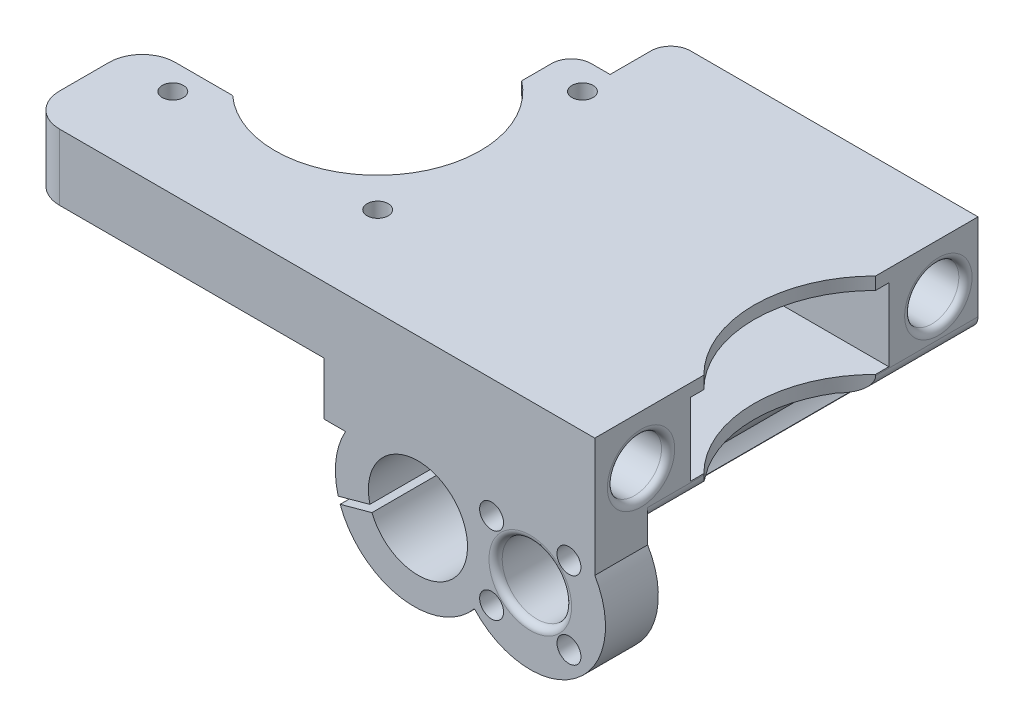
SolidWorks part; units mm, degrees
ref_plane "Alzado" through (0, 0, 0) normal (0, 0, 1) x (1, 0, 0)
ref_plane "Planta" through (0, 0, 0) normal (0, 1, 0) x (1, 0, 0)
ref_plane "Vista lateral" through (0, 0, 0) normal (1, 0, 0) x (0, 0, -1)
sketch "Croquis2" plane through (0, 0, 0) normal (0, 0, 1) x (1, 0, 0)
  line L0 (-3.0211, 10.5277) -> (-51.2966, 10.5277)
  line L2 (34.7034, 10.5277) -> (46.9364, 10.5277) construction
  line L4 (-13.6832, 10.5277) -> (-3.0211, 10.5277) construction
  line L6 (34.7034, 10.5277) -> (34.7034, 28.5277)
  line L7 (34.7034, 28.5277) -> (-51.2966, 28.5277)
  line L8 (-51.2966, 10.5277) -> (-51.2966, 28.5277)
  line L9 (-3.0211, 10.5277) -> (-13.6832, 10.5277) construction
  circle A0 centre (19.0834, 10.5277) radius 1.8114
  circle A1 centre (24.9386, 4.6724) radius 5
  circle A2 centre (30.7938, 10.5277) radius 1.8114
  circle A3 centre (19.0834, -1.1823) radius 1.81
  arc A4 (8.5391, -3.0676) -> (11.1821, 11.7271) centre (7.9425, 4.6724) ccw
  arc A5 (7.9391, -7.2159) -> (16.483, -2.9524) centre (7.3425, 4.6724) ccw
  arc A6 (34.7034, -1.1828) -> (16.483, 12.2973) centre (24.9386, 4.6724) ccw
  arc A7 (16.483, 12.2973) -> (11.7136, 15.7441) centre (7.3425, 4.6724) ccw
  arc A8 (9.846, 12.1984) -> (7.3459, -3.0676) centre (7.9425, 4.6724) ccw
  arc A9 (10.2612, 16.2123) -> (-3.0211, -1.1828) centre (7.3425, 4.6724) ccw
  circle A10 centre (30.7938, -1.1828) radius 1.8114
  arc A11 (16.483, -2.9524) -> (16.483, 12.2973) centre (24.9386, 4.6724) ccw
  arc A12 (16.483, 12.2973) -> (6.7459, -7.2159) centre (7.3425, 4.6724) ccw
  arc A13 (8.5391, -3.0676) -> (7.3459, -3.0676) centre (7.9425, 4.6724) ccw
  circle A14 centre (7.9425, 4.6724) radius 7.763
  arc A15 (16.483, 12.2973) -> (16.483, -2.9524) centre (7.3425, 4.6724) ccw
  dimension "D3" = 11.7104
  dimension "D7" = 10
  dimension "D1" = 18
  dimension "D2" = 86
  dimension "D4" = 11.7104
  dimension "D5" = 11.7104
  dimension "D6" = 11.71
extrude "Saliente-Extruir2" add sketch "Croquis2" against normal blind 58 contours A12 A7 A6 L6 L7 L8 L0 A9 | A13 A4 A5 A11 A6 A7 A12 A9 A8 A0 A1 A2 A3 A10 region at (-11.0933, 20.3038, 0) region at (16.4486, 4.6722, 0)
sketch "Croquis3" plane through (0, 0, -58) normal (0, 0, -1) x (-1, 0, 0)
  line L0 (-36.4091, 13.5277) -> (-11.0589, 13.5277) construction
  line L1 (-32.0954, 13.5277) -> (-17.7818, 13.5277)
  arc A0 (-15.2982, 10.7303) -> (-17.7818, 13.5277) centre (-24.9386, 4.6724) ccw
  arc A2 (-15.263, 10.6739) -> (-17.7818, 13.5277) centre (-24.9386, 4.6724) ccw
  circle A3 centre (-30.7938, 10.5277) radius 1.8114 construction
  circle A4 centre (-30.7938, 10.5277) radius 1.8114
  arc A5 (-32.0954, 13.5277) -> (-15.2982, -1.3854) centre (-24.9386, 4.6724) ccw
  arc A6 (-32.0954, 13.5277) -> (-15.263, -1.329) centre (-24.9386, 4.6724) ccw
  arc A7 (-15.263, 10.6739) -> (-15.263, -1.329) centre (-7.9425, 4.6724) ccw
  arc M7 (-34.7034, 10.5277) -> (-16.483, -2.9524) centre (-24.9386, 4.6724) ccw
  circle M13 centre (-19.0834, 10.5277) radius 1.8114
  circle M14 centre (-24.9386, 4.6724) radius 5
  circle M15 centre (-30.7938, 10.5277) radius 1.8114
  circle M16 centre (-19.0834, -1.1823) radius 1.81
  circle M17 centre (-30.7938, -1.1828) radius 1.8114
  dimension "D1" = 3
sketch "Croquis4" plane through (34.7034, 0, 0) normal (1, 0, 0) x (0, 0, -1)
  line L0 (0, 10.5277) -> (0, 28.5277) construction
  line L1 (58, 28.5277) -> (0, 28.5277) construction
  line L3 (14.5, 26.6277) -> (44.5, 26.6277)
  line L4 (14.5, 26.6277) -> (14.5, 15.6277)
  line L5 (14.5, 15.6277) -> (44.5, 15.6277)
  line L6 (44.5, 26.6277) -> (44.5, 15.6277)
  circle A0 centre (7, 21.0777) radius 4.1
  circle A1 centre (52, 21.0777) radius 4.1
  dimension "D3" = 7.45
  dimension "D2" = 7.45
  dimension "D1" = 7
  dimension "D4" = 45
  dimension "D5" = 30
  dimension "D6" = 11
  dimension "D7" = 1.9
  dimension "D8" = 7.5
extrude "Cortar-Extruir4" cut sketch "Croquis4" against normal blind 87 contours L6 L3 L4 L5 region at (34.7034, 21.1277, -29.5)
sketch "Croquis6" plane through (0, 10.5277, 0) normal (0, -1, 0) x (1, 0, 0)
  line L1 (-51.2966, -44.5) -> (-51.2966, -19.5)
  line L5 (-12.7902, -14.6314) -> (-17.6588, -19.5) construction
  line L6 (-51.2966, -19.5) -> (-17.6588, -19.5)
  line L7 (-51.2966, -58) -> (-51.2966, 0) construction
  line L8 (-17.6588, -19.5) -> (-17.6588, -58)
  line L9 (-3.0211, -58) -> (-51.2966, -58) construction
  line L10 (-17.6588, -58) -> (-51.2966, -58)
  line L11 (-51.2966, -58) -> (-51.2966, -19.5)
  circle A0 centre (-42.6588, -13.5) radius 1.6
  circle A1 centre (-11.6588, -13.5) radius 1.6
  circle A2 centre (-11.6588, -44.5) radius 1.6
  line M8 (-51.2966, 0) -> (-51.2966, -58)
  line M9 (-51.2966, -58) -> (-3.0211, -58)
  dimension "D1" = 31
  dimension "D4" = 6
extrude "Cortar-Extruir5" cut sketch "Croquis6" against normal blind 18 contours L8 L6 M8 M9 | A1 | A0 | A2 region at (-34.4777, 10.5277, -38.75)
sketch "Croquis7" plane through (-17.6588, 0, 0) normal (-1, 0, 0) x (0, 0, 1)
  line L0 (-19.5, 15.6277) -> (-44.5, 15.6277) construction
  line L1 (-44.5, 26.6277) -> (-41.5, 26.6277)
  line L2 (-44.5, 26.6277) -> (-44.5, 15.6277)
  line L3 (-44.5, 15.6277) -> (-41.5, 15.6277)
  line L4 (-41.5, 26.6277) -> (-41.5, 15.6277)
  dimension "D1" = 3
extrude "Saliente-Extruir3" add sketch "Croquis7" against normal blind 12
sketch "Croquis8" plane through (-51.2966, 0, 0) normal (-1, 0, 0) x (0, 0, 1)
  line L0 (-14.5, 15.6277) -> (-19.5, 15.6277) construction
  line L1 (-14.5, 26.6277) -> (-17.5, 26.6277)
  line L2 (-14.5, 26.6277) -> (-14.5, 15.6277)
  line L3 (-14.5, 15.6277) -> (-17.5, 15.6277)
  line L4 (-17.5, 26.6277) -> (-17.5, 15.6277)
  dimension "D1" = 3
extrude "Saliente-Extruir4" add sketch "Croquis8" against normal blind 45
sketch "Croquis9" plane through (-51.2966, 0, 0) normal (-1, 0, 0) x (0, 0, 1)
  line L0 (0, 10.5277) -> (0, 28.5277) construction
  line L3 (-19.5, 18.5277) -> (0, 18.5277)
  line L6 (-19.5, 18.5277) -> (0, 18.5277)
  line L7 (-19.5, 18.5277) -> (-19.5, 10.5277)
  line L8 (-19.5, 10.5277) -> (0, 10.5277)
  line L9 (0, 18.5277) -> (0, 10.5277)
  line M2 (-17.5, 26.6277) -> (-17.5, 15.6277)
  line M3 (-17.5, 15.6277) -> (-19.5, 15.6277)
  line M4 (-19.5, 15.6277) -> (-19.5, 10.5277)
  line M5 (-19.5, 10.5277) -> (0, 10.5277)
  line M6 (0, 10.5277) -> (0, 28.5277)
extrude "Cortar-Extruir6" cut sketch "Croquis9" against normal blind 45 contours L3 M2 M3 M4 M5 M6 region at (-51.2966, 14.4292, -9.4121)
sketch "Croquis10" plane through (0, 10.5277, 0) normal (0, -1, 0) x (1, 0, 0)
  line L0 (-6.2966, -19.5) -> (-17.6588, -35.5392)
  line L1 (-17.6588, -19.5) -> (-17.6588, -58) construction
  line L2 (-17.6588, -35.5392) -> (-17.6588, -19.5)
  line L3 (-17.6588, -19.5) -> (-6.2966, -19.5)
extrude "Cortar-Extruir7" cut sketch "Croquis10" against normal blind 6
sketch "Croquis11" plane through (0, 10.5277, 0) normal (0, -1, 0) x (1, 0, 0)
  line L1 (-13.5623, -58) -> (-11.8001, -58)
  line L2 (-13.5623, -48.8189) -> (-17.6588, -48.8189)
  line L3 (-13.5623, -48.8189) -> (-11.8001, -48.8189)
  line L6 (-17.6588, -35.5392) -> (-17.6588, -58) construction
  line L7 (-17.6588, -48.8189) -> (-17.6588, -58)
  line L8 (-17.6588, -58) -> (-13.5623, -58)
  line L9 (-11.8001, -48.8189) -> (-11.8001, -58)
extrude "Cortar-Extruir8" cut sketch "Croquis11" against normal blind 18
sketch "Croquis12" plane through (-51.2966, 0, 0) normal (-1, 0, 0) x (0, 0, 1)
  line L1 (-19.5, 28.5277) -> (-17.5, 28.5277)
  line L2 (-19.5, 28.5277) -> (-19.5, 26.6277)
  line L3 (-19.5, 26.6277) -> (-17.5, 26.6277)
  line L4 (-17.5, 28.5277) -> (-17.5, 26.6277)
extrude "Cortar-Extruir9" cut sketch "Croquis12" against normal up to vertex (33.6377 mm away) up to point (-17.6588, 26.6277, -19.5)
sketch "Croquis13" plane through (0, 28.5277, 0) normal (0, 1, 0) x (1, 0, 0)
  line L3 (-28.256, 13.5) -> (-26.0617, 13.5) construction
  circle A6 centre (-27.1588, 29) radius 15.5388
extrude "Cortar-Extruir10" cut sketch "Croquis13" against normal up to vertex (12.9 mm away) up to point (-17.6588, 15.6277, -35.5392)
sketch "Croquis15" plane through (0, 28.5277, 0) normal (0, 1, 0) x (1, 0, 0)
  circle A0 centre (-11.6588, 44.5) radius 1.6 construction
  circle A1 centre (-11.6588, 13.5) radius 1.6 construction
  circle A2 centre (-42.6588, 13.5) radius 1.6 construction
  circle A3 centre (-11.6588, 44.5) radius 1.6
  circle A4 centre (-11.6588, 13.5) radius 1.6
  circle A5 centre (-42.6588, 13.5) radius 1.6
extrude "Cortar-Extruir11" cut sketch "Croquis15" against normal up to surface (18 mm away) up to face at (-10.0588, 10.5277, -44.5)
sketch "Croquis16" plane through (0, 18.5277, 0) normal (0, -1, 0) x (1, 0, 0)
  circle A0 centre (-11.6588, -13.5) radius 3
  circle A1 centre (-42.6588, -13.5) radius 3
  dimension "D1" = 6
  dimension "D2" = 6
extrude "Cortar-Extruir12" cut sketch "Croquis16" against normal blind 4
sketch "Croquis17" plane through (0, 10.5277, 0) normal (0, -1, 0) x (1, 0, 0)
  circle A0 centre (-11.6588, -44.5) radius 2.95
  dimension "D1" = 5.9
extrude "Cortar-Extruir16" cut sketch "Croquis3" against normal blind 50 contours A7 A2 A0 L1 A5 A6 M7 M13 M15 M17 M16 M14 region at (24.9386, 13.2355, -58)
sketch "Croquis18" plane through (34.7034, 0, 0) normal (1, 0, 0) x (0, 0, -1)
  circle A0 centre (7, 21.0777) radius 4.1
  circle A1 centre (52, 21.0777) radius 4.1
extrude "Cortar-Extruir17" cut sketch "Croquis18" against normal blind 42
sketch "Croquis19" plane through (0, 28.5277, 0) normal (0, 1, 0) x (1, 0, 0)
  line L0 (34.7034, 58) -> (34.7034, 42.5) construction
  line L1 (34.7034, 58) -> (34.7034, 0) construction
  line L2 (34.7034, 0) -> (34.7034, 16.5) construction
  arc A0 (34.7034, 42.5) -> (34.7034, 16.5) centre (47.7034, 29.5) ccw
  dimension "D1" = 16.5
  dimension "D2" = 15.5
extrude "Cortar-Extruir19" cut sketch "Croquis19" against normal blind 19 and the other way through all
fillet "Redondeo1" radius 5 3 edges at (-51.2966, 23.5277, -17.5) (-6.2966, 22.5777, -17.5) (-5.6588, 21.1277, -41.5)
fillet "Redondeo2" radius 5 1 edges at (-51.2966, 23.5277, 0)
fillet "Redondeo3" radius 2 2 edges at (34.7034, 10.5277, -12.25) (34.7034, 10.5277, -50.25)
fillet "Redondeo4" radius 1 2 edges at (34.7034, 21.0777, -11.1) (34.7034, 21.0777, -56.1)
sketch "Croquis20" plane through (0, 0, -58) normal (0, 0, -1) x (-1, 0, 0)
  circle A0 centre (-7.9425, 4.6724) radius 7.763 construction
  circle A1 centre (-7.9425, 4.6724) radius 7.763
  circle A2 centre (-7.9425, 4.6724) radius 7.5
  dimension "D1" = 15
extrude "Saliente-Extruir5" add sketch "Croquis20" against normal up to surface (58 mm away) up to face at (20.8948, 10.5277, 0)
sketch "Croquis21" plane through (0, 0, -58) normal (0, 0, -1) x (-1, 0, 0)
  line L0 (-0.6734, 2.8256) -> (4.129, 1.4956)
  line L1 (3.8352, 0.58) -> (-0.9757, 1.8951)
  circle A2 centre (-7.9425, 4.6724) radius 7.5 construction
  arc A3 (-16.483, -2.9524) -> (3.0211, 10.5277) centre (-7.3425, 4.6724) ccw construction
  arc A4 (-0.9757, 1.8951) -> (-0.6734, 2.8256) centre (-7.9425, 4.6724) ccw
  arc A5 (3.8352, 0.58) -> (4.129, 1.4956) centre (-7.3425, 4.6724) ccw
extrude "Cortar-Extruir20" cut sketch "Croquis21" against normal up to vertex (58 mm away) up to point (16.483, -2.9524, 0)
sketch "Croquis22" plane through (0, 0, -8) normal (0, 0, -1) x (-1, 0, 0)
  circle A0 centre (-24.9386, 4.6724) radius 5 construction
  circle A1 centre (-24.9386, 4.6724) radius 5
  circle A2 centre (-24.9386, 4.6724) radius 5.25
  dimension "D1" = 10.5
extrude "Cortar-Extruir21" cut sketch "Croquis22" against normal up to surface (8 mm away) up to face at (-0.8485, 10.0116, 0)
fillet "Redondeo6" radius 1 1 edges at (30.1886, 4.6724, 0)
extrude "Cortar-Extruir22" cut sketch "Croquis17" against normal blind 12
sketch "Croquis23" plane through (0, 0, -58) normal (0, 0, -1) x (-1, 0, 0)
  line L1 (3.0211, 10.5277) -> (9.0211, 10.5277)
  line L2 (3.0211, 10.5277) -> (3.0211, 4.5277)
  line L3 (3.0211, 4.5277) -> (9.0211, 4.5277)
  line L4 (9.0211, 10.5277) -> (9.0211, 4.5277)
  arc A0 (4.129, 1.4956) -> (3.0211, 10.5277) centre (-7.3425, 4.6724) ccw construction
  dimension "D1" = 6
  dimension "D2" = 6
extrude "Saliente-Extruir6" add sketch "Croquis23" against normal blind 8
sketch "Croquis24" plane through (0, 0, -58) normal (0, 0, -1) x (-1, 0, 0)
  line L0 (4.0211, 4.5277) -> (10.0211, 10.5277) construction
  line L1 (9.0211, 4.5277) -> (9.0211, 10.5277) construction
  circle A0 centre (7.0211, 7.5277) radius 1.45
  dimension "D1" = 2
extrude "Cortar-Extruir23" cut sketch "Croquis24" against normal up to vertex (8 mm away) up to point (-4.5599, 4.5277, -50)
fillet "Redondeo7" radius 3 2 edges at (-11.8001, 19.5277, -58) (-17.6588, 19.5277, -48.8189)
fillet "Redondeo8" radius 2 1 edges at (-9.0211, 4.5277, -53.9959)
